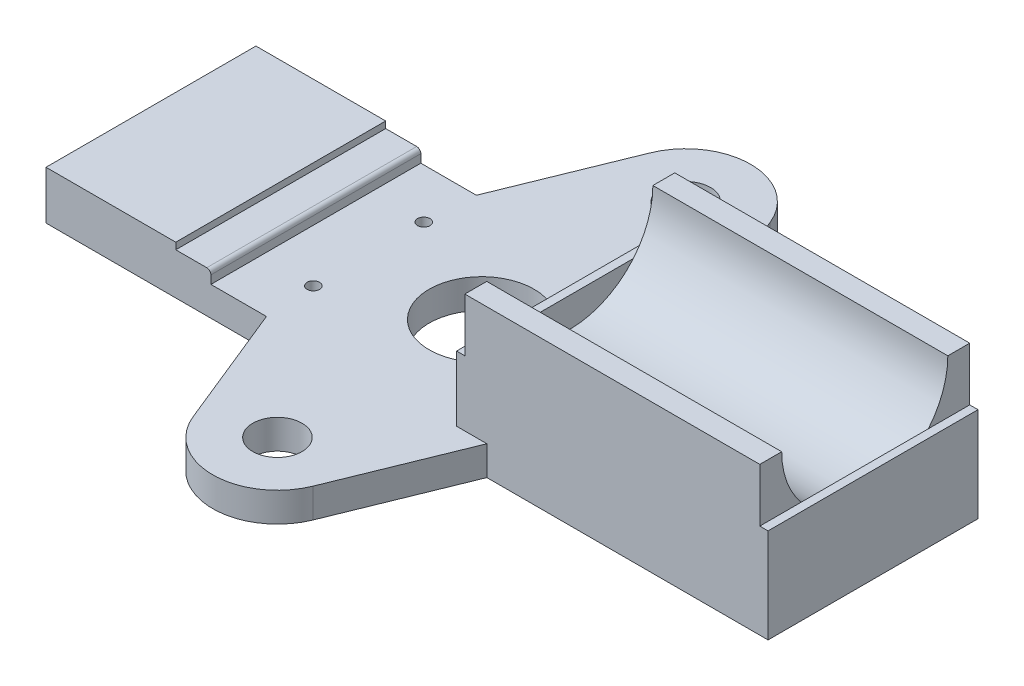
SolidWorks part; units mm, degrees
ref_plane "Front Plane" through (0, 0, 0) normal (0, 0, 1) x (1, 0, 0)
ref_plane "Top Plane" through (0, 0, 0) normal (0, 1, 0) x (1, 0, 0)
ref_plane "Right Plane" through (0, 0, 0) normal (1, 0, 0) x (0, 0, -1)
sketch "Sketch1" plane through (0, 0, 0) normal (0, 1, 0) x (1, 0, 0)
  line L1 (-86.36, 25.4) -> (86.36, 25.4)
  line L2 (-86.36, 25.4) -> (-86.36, -25.4)
  line L3 (-86.36, -25.4) -> (86.36, -25.4)
  line L4 (86.36, 25.4) -> (86.36, -25.4)
  line L5 (-86.36, 25.4) -> (86.36, -25.4) construction
  line L6 (-86.36, -25.4) -> (86.36, 25.4) construction
  point P0 (0, 0)
  dimension "D1" = 172.72
  dimension "D2" = 50.8
extrude "Boss-Extrude1" add sketch "Sketch1" along normal blind 12.7
sketch "Sketch2" plane through (0, 0, 0) normal (0, -1, 0) x (1, 0, 0)
  point P0 (-87.3294, -20.744)
sketch "Sketch4" plane through (86.36, 0, 0) normal (1, 0, 0) x (0, 0, -1)
  line L0 (-25.4, 12.7) -> (-25.4, 35.8)
  line L1 (25.4, 35.8) -> (25.4, 12.7)
  line L2 (-25.4, 35.8) -> (-20.1, 35.8)
  line L3 (25.4, 35.8) -> (20.1, 35.8)
  line L4 (-25.4, 12.7) -> (25.4, 12.7) construction
  line L5 (-25.4, 12.7) -> (25.4, 12.7)
  arc A0 (20.1, 35.8) -> (-20.1, 35.8) centre (0, 35.8) cw
  dimension "D1" = 20.1
  dimension "D2" = 3
extrude "Boss-Extrude2" add sketch "Sketch4" against normal blind 71.374
sketch "Sketch5" plane through (86.36, 0, 0) normal (1, 0, 0) x (0, 0, -1)
  line L0 (25.4, 35.8) -> (25.4, 0) construction
  line L1 (-25.4, 0) -> (25.4, 0)
  line L2 (-25.4, 0) -> (-25.4, 22.86)
  line L3 (-25.4, 22.86) -> (25.4, 22.86)
  line L4 (25.4, 0) -> (25.4, 22.86)
  dimension "D1" = 22.86
extrude "Boss-Extrude3" add sketch "Sketch5" along normal blind 2
sketch "Sketch6" plane through (14.986, 0, 0) normal (-1, 0, 0) x (0, 0, 1)
  line L1 (-25.4, 12.7) -> (25.4, 12.7)
  line L2 (-25.4, 12.7) -> (-25.4, 22.86)
  line L3 (-25.4, 22.86) -> (25.4, 22.86)
  line L4 (25.4, 12.7) -> (25.4, 22.86)
extrude "Boss-Extrude4" add sketch "Sketch6" along normal blind 2
sketch "Sketch7" plane through (0, 0, 25.4) normal (0, 0, 1) x (1, 0, 0)
  line L0 (-86.36, 12.7) -> (-86.36, 11.7)
  line L1 (-86.36, 12.7) -> (-86.36, 0) construction
  line L2 (-86.36, 11.7) -> (-54.96, 11.7)
  line L3 (-54.96, 11.7) -> (-54.96, 10.1)
  line L4 (-54.96, 10.1) -> (-46.46, 10.1)
  line L5 (-46.46, 10.1) -> (-46.46, 7.1)
  line L6 (-46.46, 7.1) -> (12.986, 7.1)
  line L7 (12.986, 7.1) -> (12.986, 12.7)
  line L8 (-86.36, 12.7) -> (12.986, 12.7) construction
  line L9 (12.986, 12.7) -> (-86.36, 12.7)
  line L10 (12.986, 12.7) -> (12.986, 22.86) construction
  dimension "D1" = 1
  dimension "D2" = 31.4
  dimension "D3" = 1.6
  dimension "D4" = 8.5
  dimension "D5" = 3
extrude "Cut-Extrude1" cut sketch "Sketch7" against normal through all
fillet "Fillet1" radius 1 1 edges at (-46.46, 10.1, 0)
sketch "Sketch8" plane through (0, 0, 0) normal (0, -1, 0) x (1, 0, 0)
  circle A0 centre (-6.35, 0) radius 12.7
  point P3 (-13.5634, 0)
  point P5 (0, 0)
  dimension "D1" = 25.4
  dimension "D2" = 6.35
extrude "Cut-Extrude2" cut sketch "Sketch8" against normal up to surface (7.1 mm away) contours A0 up to face at (-16.737, 7.1, 0)
sketch "Sketch9" plane through (0, 0, 0) normal (0, 1, 0) x (1, 0, 0)
  line L0 (-33.02, 25.4) -> (-20.875, 55.3088)
  line L1 (-46.46, 25.4) -> (12.986, 25.4) construction
  line L2 (8.175, 55.3088) -> (20.32, 25.4)
  line L3 (14.986, 25.4) -> (86.36, 25.4) construction
  line L4 (20.32, 25.4) -> (-33.02, 25.4)
  line L5 (-19.69, 0) -> (19.69, 0) construction
  line L6 (20.32, -25.4) -> (-33.02, -25.4)
  line L7 (8.175, -55.3088) -> (20.32, -25.4)
  line L8 (-33.02, -25.4) -> (-20.875, -55.3088)
  arc A0 (-20.875, 55.3088) -> (8.175, 55.3088) centre (-6.35, 49.4106) cw
  circle A1 centre (-6.35, 49.4106) radius 5.9563
  circle A2 centre (-6.35, -49.4106) radius 5.9563
  arc A3 (-20.875, -55.3088) -> (8.175, -55.3088) centre (-6.35, -49.4106) ccw
  point P11 (-6.35, 0)
  dimension "D1" = 15.6769
  dimension "D4" = 11.9126
  dimension "D2" = 39.6875
  dimension "D3" = 53.34
extrude "Boss-Extrude5" add sketch "Sketch9" along normal up to surface (7.1 mm away) up to face at (-6.35, 7.1, -12.7)
sketch "Sketch10" plane through (0, 7.1, 0) normal (0, 1, 0) x (1, 0, 0)
  line L0 (-46.46, 25.4) -> (-46.46, -25.4) construction
  line L1 (-46.46, -25.4) -> (-33.02, -25.4) construction
  line L2 (-46.46, 25.4) -> (-33.02, 25.4) construction
  circle A0 centre (-33.76, 13.41) radius 1.5
  circle A1 centre (-33.76, -13.31) radius 1.5
  point P0 (-33.76, 13.41)
  point P1 (-33.76, -13.31)
  point P14 (0, 0)
  dimension "D1" = 3
  dimension "D2" = 12.7
  dimension "D3" = 12.09
  dimension "D4" = 11.99
extrude "Cut-Extrude3" cut sketch "Sketch10" against normal up to surface (7.1 mm away) up to face at (-6.35, 0, -12.7)
